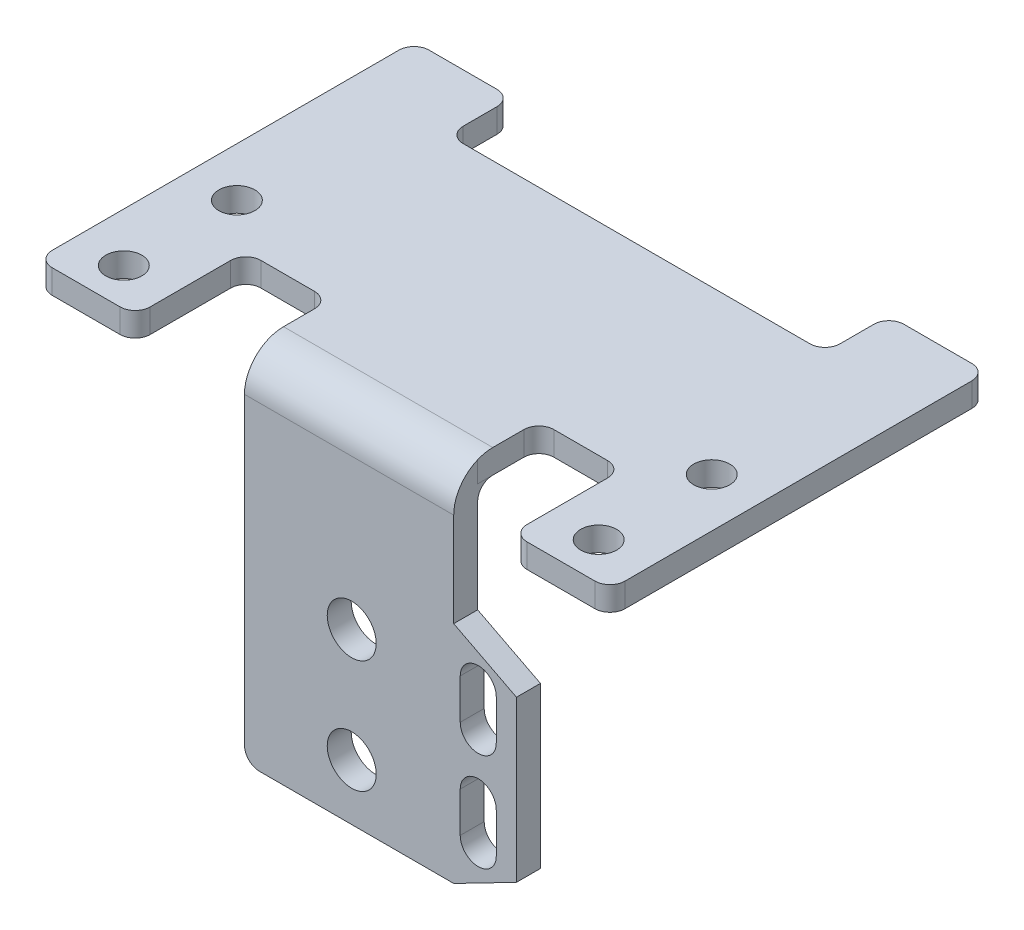
SolidWorks part; units mm, degrees
ref_plane "Front" through (0, 0, 0) normal (0, 0, 1) x (1, 0, 0)
ref_plane "Top" through (0, 0, 0) normal (0, 1, 0) x (1, 0, 0)
ref_plane "Right" through (0, 0, 0) normal (1, 0, 0) x (0, 0, -1)
sketch "Sketch1" plane through (0, 0, 0) normal (0, 1, 0) x (1, 0, 0)
  line L0 (0, 0) -> (0, 50)
  line L1 (0, 50) -> (13, 50)
  line L2 (13, 50) -> (13, 41.5219)
  line L3 (13, 41.5219) -> (63, 41.5219)
  line L4 (63, 41.5219) -> (63, 50)
  line L5 (63, 50) -> (76, 50)
  line L6 (76, 50) -> (76, 0)
  line L7 (76, 0) -> (63, 0)
  line L8 (63, 0) -> (63, 14.6853)
  line L9 (63, 14.6853) -> (51.88, 14.6853)
  line L10 (13, 14.6853) -> (13, 0)
  line L11 (13, 0) -> (0, 0)
  line L12 (24.12, 14.6853) -> (24.12, 6.5669)
  line L13 (24.12, 6.5669) -> (51.88, 6.5669)
  line L14 (51.88, 6.5669) -> (51.88, 14.6853)
  line L16 (24.12, 14.6853) -> (13, 14.6853)
  dimension "D1" = 76
  dimension "D2" = 13
  dimension "D3" = 13
  dimension "D4" = 27.76
  dimension "D5" = 50
  dimension "D6" = 8.4781
extrude "Boss-Extrude2" add sketch "Sketch1" against normal blind 3.18
sketch "Sketch8" plane through (0, 0, -6.5669) normal (0, 0, 1) x (1, 0, 0)
  line L0 (24.12, -45.5) -> (24.12, -20.1534)
  line L2 (51.8796, -17.65) -> (60.2044, -21.94)
  line L3 (60.2044, -21.94) -> (60.2044, -43.21)
  line L4 (60.2044, -43.21) -> (51.8796, -47.5)
  line L8 (51.8796, -47.5) -> (26.12, -47.5)
  line L12 (51.8796, 0) -> (51.8796, -17.65)
  line L13 (24.12, -20.1534) -> (24.12, 0)
  line L14 (24.12, 0) -> (51.8796, 0)
  line L15 (55.1344, -23.2235) -> (55.1344, -28.5469) construction
  line L16 (57.5244, -23.2235) -> (57.5244, -28.5469)
  line L17 (52.7444, -23.2235) -> (52.7444, -28.5469)
  line L18 (55.1344, -36.2235) -> (55.1344, -41.5469) construction
  line L19 (57.5244, -36.2235) -> (57.5244, -41.5469)
  line L20 (52.7444, -36.2235) -> (52.7444, -41.5469)
  line L27 (13, -3.18) -> (13, 0) construction
  circle A0 centre (38.3488, -25.08) radius 3.25
  circle A1 centre (38.3488, -40.08) radius 3.25
  arc A3 (57.5244, -23.2235) -> (52.7444, -23.2235) centre (55.1344, -23.2235) ccw
  arc A4 (52.7444, -28.5469) -> (57.5244, -28.5469) centre (55.1344, -28.5469) ccw
  arc A5 (57.5244, -36.2235) -> (52.7444, -36.2235) centre (55.1344, -36.2235) ccw
  arc A6 (52.7444, -41.5469) -> (57.5244, -41.5469) centre (55.1344, -41.5469) ccw
  arc A7 (26.12, -47.5) -> (24.12, -45.5) centre (26.12, -45.5) cw
  point P19 (55.1344, -25.8852)
  point P24 (55.1344, -38.8852)
  dimension "D7" = 2
  dimension "D1" = 47.5
  dimension "D2" = 21.27
  dimension "D3" = 29.85
  dimension "D4" = 2.68
  dimension "D5" = 15
  dimension "D6" = 7.42
  dimension "D8" = 11.12
  dimension "D9" = 27.7596
extrude "Boss-Extrude3" add sketch "Sketch8" along normal blind 3.18
fillet "Fillet4" radius 5.18 1 edges at (37.9998, 0, -3.3869)
fillet "Fillet5" radius 2 1 edges at (37.9998, -3.18, -6.5669)
sketch "Sketch9" plane through (0, 0, 0) normal (0, 1, 0) x (1, 0, 0)
  line L1 (0, 50) -> (0, 0) construction
  line L2 (0, 0) -> (13, 0) construction
  circle A0 centre (6.5, 5) radius 2.39
  circle A1 centre (6.5, 20) radius 2.39
  circle A2 centre (69.5, 20) radius 2.39
  circle A3 centre (69.5, 5) radius 2.39
  dimension "D1" = 4.78
  dimension "D2" = 15
  dimension "D3" = 6.5
  dimension "D4" = 6.5
  dimension "D5" = 5
extrude "Cut-Extrude1" cut sketch "Sketch9" against normal blind 3.18
fillet "Fillet6" radius 2 1 edges at (0, -1.59, 0)
fillet "Fillet7" radius 2 1 edges at (13, -1.59, 0)
fillet "Fillet8" radius 2 12 edges at (51.88, -1.59, -14.6853) (13, -1.59, -14.6853) (13, -1.59, -41.5219) (63, -1.59, -41.5219) (76, -1.59, -50) (63, -1.59, -50) (0, -1.59, -50) (13, -1.59, -50) (63, -1.59, -14.6853) (24.12, -1.59, -14.6853) (76, -1.59, 0) (63, -1.59, 0)
sketch "Sketch4" [suppressed] plane through (0, 0, 0) normal (0, 0, 1) x (1, 0, 0)
  line L0 (-14.0978, 0) -> (-14.0978, 45)
  line L1 (-11.5978, 47.5) -> (13.6618, 47.5)
  line L2 (13.6618, 47.5) -> (21.2228, 43.2094)
  line L3 (21.2228, 43.2094) -> (21.2228, 21.944)
  line L4 (21.2228, 21.944) -> (13.6618, 17.6534)
  line L5 (13.6618, 17.6534) -> (13.6618, 3.18)
  line L6 (13.6618, 3.18) -> (13.6618, 0)
  line L7 (13.6618, 0) -> (-14.0978, 0)
  arc A0 (-11.5978, 47.5) -> (-14.0978, 45) centre (-11.5978, 45) ccw
  dimension "D1" = 2.5
  dimension "D2" = 45
sketch "Sketch3" [suppressed] plane through (0, 0, 0) normal (0, 0, 1) x (1, 0, 0)
  circle A0 centre (-0.2978, 40.0831) radius 3.25
  circle A1 centre (-0.2978, 25.0831) radius 3.25
  dimension "D1" = 6.5
  dimension "D2" = 6.5
  dimension "D3" = 15
sketch "Sketch5" [suppressed] plane through (0, 0, 0) normal (0, 0, 1) x (1, 0, 0)
  line L0 (16.1496, 41.3556) -> (16.1496, 36.0322) construction
  line L1 (18.5396, 41.3556) -> (18.5396, 36.0322)
  line L2 (13.7596, 41.3556) -> (13.7596, 36.0322)
  line L3 (16.1496, 28.3556) -> (16.1496, 23.0322) construction
  line L4 (18.5396, 28.3556) -> (18.5396, 23.0322)
  line L5 (13.7596, 28.3556) -> (13.7596, 23.0322)
  arc A0 (18.5396, 41.3556) -> (13.7596, 41.3556) centre (16.1496, 41.3556) ccw
  arc A1 (13.7596, 36.0322) -> (18.5396, 36.0322) centre (16.1496, 36.0322) ccw
  arc A2 (18.5396, 28.3556) -> (13.7596, 28.3556) centre (16.1496, 28.3556) ccw
  arc A3 (13.7596, 23.0322) -> (18.5396, 23.0322) centre (16.1496, 23.0322) ccw
  point P2 (16.1496, 38.6939)
  point P7 (16.1496, 25.6939)
  dimension "D1" = 4.78
  dimension "D2" = 4.78
  dimension "D3" = 13
